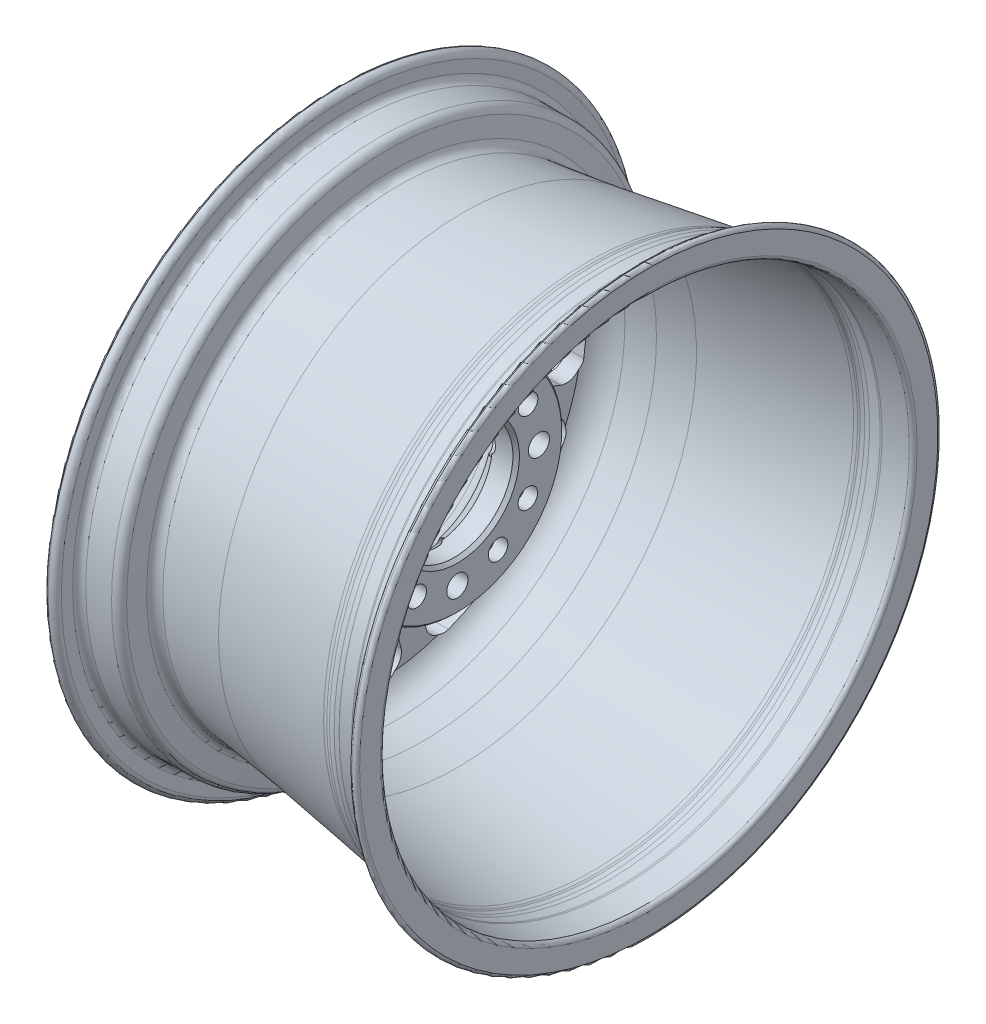
SolidWorks part; units mm, degrees
material "6061 Alloy"
ref_plane "Front Plane" through (0, 0, 0) normal (0, 0, 1) x (1, 0, 0)
ref_plane "Top Plane" through (0, 0, 0) normal (0, 1, 0) x (1, 0, 0)
ref_plane "Right Plane" through (0, 0, 0) normal (1, 0, 0) x (0, 0, -1)
sketch "Sketch1" plane through (0, 0, 0) normal (0, 0, 1) x (1, 0, 0)
  line L0 (0, 0) -> (33164.3274, 0) construction
  line L1 (0, 0) -> (0, 33164.3274) construction
  line L2 (0.0368, 178.325) -> (0.0368, 165.9849)
  line L3 (3.6882, 162.0001) -> (23.2459, 160.2891)
  line L7 (1.5368, 179.825) -> (1.8368, 179.825)
  line L8 (5.8368, 175.825) -> (5.8368, 168.825)
  line L9 (9.8368, 164.825) -> (25.6368, 164.825)
  line L19 (184.6368, 172.1546) -> (184.6368, 174.836)
  line L21 (190.6368, 177.4874) -> (190.6368, 164.7286)
  line L26 (177.3341, 164.185) -> (172.7295, 163.7822)
  line L38 (30.5561, 160.4872) -> (31.9381, 149.53)
  line L39 (37.5245, 145.195) -> (51.4368, 146.9497)
  line L42 (27.7745, 155.9302) -> (29.0697, 145.6607)
  line L43 (34.6561, 141.3257) -> (51.8723, 143.4971)
  line L46 (51.4368, 146.9497) -> (51.8723, 143.4971) construction
  line L47 (51.4368, 146.9497) -> (76.6368, 150.1281)
  line L48 (51.8723, 143.4971) -> (72.8792, 147.0647)
  line L49 (172.0635, 163.7795) -> (164.9558, 164.3453)
  line L51 (164.8368, 164.35) -> (161.8368, 164.35)
  line L52 (158.2699, 163.6704) -> (155.5589, 162.5984)
  line L53 (153.0338, 162.002) -> (76.6368, 150.1281)
  line L59 (177.5868, 161.296) -> (172.9823, 160.8932) construction
  line L60 (188.3547, 162.2381) -> (172.9823, 160.8932)
  line L61 (171.8334, 160.8887) -> (164.7812, 161.45)
  line L62 (164.7812, 161.45) -> (161.8368, 161.45)
  line L63 (159.3363, 160.9736) -> (158.3066, 160.5664)
  line L64 (156.3794, 160.0426) -> (72.8792, 147.0647)
  line L65 (153.4101, 159.5811) -> (77.0131, 147.7072) construction
  line L66 (159.3363, 160.9736) -> (156.6253, 159.9016) construction
  arc A0 (190.6368, 164.7286) -> (188.3547, 162.2381) centre (188.1368, 164.7286) cw
  arc A1 (184.6368, 172.1546) -> (177.3341, 164.185) centre (176.6368, 172.1546) cw
  arc A2 (187.9279, 179.4286) -> (184.6368, 174.836) centre (189.4868, 174.836) ccw
  arc A3 (187.9279, 179.4286) -> (190.6368, 177.4874) centre (188.5868, 177.4874) cw
  arc A12 (37.5245, 145.195) -> (31.9381, 149.53) centre (36.8988, 150.1557) cw
  arc A13 (30.5561, 160.4872) -> (25.6368, 164.825) centre (25.6368, 159.8668) ccw
  arc A14 (3.6882, 162.0001) -> (0.0368, 165.9849) centre (4.0368, 165.9849) cw
  arc A15 (9.8368, 164.825) -> (5.8368, 168.825) centre (9.8368, 168.825) cw
  arc A16 (1.8368, 179.825) -> (5.8368, 175.825) centre (1.8368, 175.825) cw
  arc A17 (1.5368, 179.825) -> (0.0368, 178.325) centre (1.5368, 178.325) ccw
  arc A20 (34.6561, 141.3257) -> (29.0697, 145.6607) centre (34.0304, 146.2864) cw
  arc A21 (27.7745, 155.9302) -> (23.2459, 160.2891) centre (22.8097, 155.304) ccw
  arc A22 (172.7295, 163.7822) -> (172.0635, 163.7795) centre (172.3809, 167.7669) cw
  arc A23 (164.9558, 164.3453) -> (164.8368, 164.35) centre (164.8368, 162.85) ccw
  arc A24 (161.8368, 164.35) -> (158.2699, 163.6704) centre (161.8368, 154.65) ccw
  arc A25 (155.5589, 162.5984) -> (153.0338, 162.002) centre (152.2494, 170.9678) cw
  arc A30 (172.9823, 160.8932) -> (171.8334, 160.8887) centre (172.3809, 167.7669) cw
  arc A31 (164.7812, 161.45) -> (164.7812, 161.45) centre (164.7812, 161.45) ccw
  arc A32 (161.8368, 161.45) -> (159.3363, 160.9736) centre (161.8368, 154.65) ccw
  arc A33 (156.3794, 160.0426) -> (158.3066, 160.5664) centre (154.9972, 168.9358) ccw
  arc A34 (156.6253, 159.9016) -> (153.2865, 159.1131) centre (152.2494, 170.9678) cw construction
  point P10 (37.7809, 148.545)
  point P22 (184.6493, 164.825)
  point P32 (172.3966, 163.753)
  point P35 (164.8964, 164.35)
  point P40 (159.9886, 164.35)
  dimension "D15" = 2.5
  dimension "D16" = 8
  dimension "D17" = 9.7
  dimension "D12" = 2.05
  dimension "D23" = 14.7
  dimension "D24" = 9
  dimension "D25" = 328.7
  dimension "D8" = 19.8
  dimension "D9" = 3
  dimension "D10" = 4
  dimension "D29" = 2.45
  dimension "D7" = 114
  dimension "D5" = 4
  dimension "D6" = 4
  dimension "D40" = 4
  dimension "D41" = 1.5
  dimension "D33" = 2.45
  dimension "D21" = 1.5
  dimension "D22" = 9.7
  dimension "D31" = 9
  dimension "D1" = 5.8
  dimension "D4" = 5
  dimension "D13" = 6
  dimension "D14" = 329.65
  dimension "D18" = 178.8
  dimension "D19" = 85
  dimension "D20" = 328.37
  dimension "D30" = 2.9
  dimension "D34" = 139.2
  dimension "D35" = 3.33
  dimension "D36" = 3.48
  dimension "D45" = 15
  dimension "D46" = 329.65
  dimension "D47" = 3.35
  dimension "D48" = 19.8
  dimension "D49" = 19.63
revolve "Revolve1" add sketch "Sketch1" angle 360 about L0
ref_plane "Plane1" through (73.2368, 0, 0) normal (1, 0, 0) x (0, 0, -1)
sketch "Sketch2" plane through (0, 0, 0) normal (0, 1, 0) x (1, 0, 0)
  line L0 (0, 0) -> (50000, 0) construction
  line L1 (0, 0) -> (0, 50000) construction
  line L2 (71.2368, 36) -> (58.7368, 36)
  line L3 (58.7368, 36) -> (48.2368, 46.5)
  line L4 (73.2368, 38) -> (73.2368, 64)
  line L5 (72.2368, 65) -> (69.5683, 65)
  line L6 (29.0697, 145.6607) -> (27.7745, 155.9302) construction
  line L8 (190.6368, -177.4874) -> (190.6368, 177.4874) construction
  line L9 (73.2368, 38) -> (71.2368, 36)
  line L10 (29.0697, 145.6607) -> (27.7745, 155.9302)
  line L12 (9.5426, 131.4781) -> (19.6126, 130.5865) construction
  line L18 (73.2368, 64) -> (72.2368, 65)
  line L20 (48.2368, 46.5) -> (19.7321, 75.0047) construction
  line L22 (9.5426, 131.4781) -> (5.7113, 88.2067)
  line L23 (17.262, 68.2791) -> (34.319, 60.4178)
  line L26 (5.7113, 88.2067) -> (23.9783, 88.2067) construction
  line L28 (19.6126, 130.5865) -> (20.6039, 98.7163)
  line L31 (32.4138, 81.0877) -> (67.5326, 65.4332)
  arc A1 (29.0697, 145.6607) -> (34.6561, 141.3257) centre (34.0304, 146.2864) ccw construction
  arc A2 (27.8741, 155.1399) -> (27.7745, 155.9302) centre (21.8846, 154.7859) ccw
  arc A3 (29.0697, 145.6607) -> (34.6561, 141.3257) centre (34.0304, 146.2864) ccw
  arc A8 (9.5426, 131.4781) -> (24.7302, 148.6092) centre (37.9429, 121.5976) cw
  arc A9 (24.7302, 148.6092) -> (27.7745, 155.9302) centre (22.0938, 153.999) ccw
  arc A10 (48.2368, 46.5) -> (34.319, 60.4178) centre (22.4209, 34.6019) ccw
  arc A11 (5.7113, 88.2067) -> (17.262, 68.2791) centre (25.6333, 86.4428) ccw
  arc A12 (34.6561, 141.3257) -> (19.6126, 130.5865) centre (37.4396, 121.5203) ccw
  arc A13 (20.6039, 98.7163) -> (32.4138, 81.0877) centre (40.5942, 99.3382) ccw
  arc A16 (69.5683, 65) -> (67.5326, 65.4332) centre (69.5683, 70) cw
  point P5 (73.2368, 36)
  point P9 (73.2368, 65)
  point P25 (10.3832, 133.6254)
  point P32 (37.9429, 121.5976)
  point P41 (33.0012, 151.2587)
  point P48 (23.9783, 88.2067)
  dimension "D11" = 262.9563
  dimension "D12" = 28.4258
  dimension "D13" = 20
  dimension "D14" = 6
  dimension "D15" = 5
  dimension "D19" = 12
  dimension "D20" = 20
  dimension "D21" = 20
  dimension "D1" = 117.4
  dimension "D2" = 72
  dimension "D3" = 45
  dimension "D4" = 2
  dimension "D5" = 45
  dimension "D6" = 130
  dimension "D7" = 25
  dimension "D8" = 10.5
  dimension "D9" = 1
  dimension "D10" = 45
  dimension "D17" = 10.07
revolve "Revolve2" add sketch "Sketch2" angle 360 about L0 region at (64.9868, 0, -37.3559)
sketch "Sketch4" plane through (73.2368, 0, 0) normal (1, 0, 0) x (0, 0, -1)
  line L0 (0, 0) -> (0, -50000) construction
  line L1 (0, 0) -> (-50000, 0) construction
  line L2 (0, 0) -> (-43301.2702, -25000) construction
  line L3 (0, 0) -> (-48296.2913, -12940.9523) construction
  line L4 (0, 0) -> (-35355.3391, -35355.3391) construction
  line L5 (0, 0) -> (-48296.2913, 12940.9523) construction
  line L6 (-94.6782, 94.3597) -> (294.6551, 94.3597) construction
  line L7 (-112.377, -43.4279) -> (-80.0541, -34.9429)
  line L8 (-80.0541, -34.9429) -> (-80.051, -34.9527) construction
  line L9 (-93.7982, -75.6073) -> (-70.2885, -51.8574)
  line L10 (-116.4914, 28.3198) -> (-88.8855, 16.2865)
  line L11 (-116.4914, -28.3198) -> (-88.8855, -16.2865)
  line L12 (-33.72, 115.0444) -> (-30.3383, 85.1204)
  line L13 (-82.7713, 86.7246) -> (-58.5473, 68.8339)
  line L14 (-93.7982, 75.6073) -> (-70.2885, 51.8574)
  line L15 (-112.377, 43.4279) -> (-80.0541, 34.9429)
  line L16 (82.7713, 86.7246) -> (58.5473, 68.8339)
  line L17 (33.72, 115.0444) -> (30.3383, 85.1204)
  line L18 (18.5788, 119.0353) -> (9.7656, 86.8003)
  line L19 (-18.5788, 119.0353) -> (-9.7656, 86.8003)
  line L20 (116.4914, -28.3198) -> (88.8855, -16.2865)
  line L21 (116.4914, 28.3198) -> (88.8855, 16.2865)
  line L22 (112.377, 43.4279) -> (80.0541, 34.9429)
  line L23 (93.7982, 75.6073) -> (70.2885, 51.8574)
  line L24 (33.72, -115.0444) -> (30.3383, -85.1204)
  line L25 (82.7713, -86.7246) -> (58.5473, -68.8339)
  line L26 (93.7982, -75.6073) -> (70.2885, -51.8574)
  line L27 (112.377, -43.4279) -> (80.0541, -34.9429)
  line L28 (-82.7713, -86.7246) -> (-58.5473, -68.8339)
  line L29 (-33.72, -115.0444) -> (-30.3383, -85.1204)
  line L30 (-18.5788, -119.0353) -> (-9.7656, -86.8003)
  line L31 (18.5788, -119.0353) -> (9.7656, -86.8003)
  line L32 (-18.5788, -119.0353) -> (-9.7656, -86.8003) [skipped]
  line L33 (18.5788, -119.0353) -> (9.7656, -86.8003) [skipped]
  line L34 (93.7982, -75.6073) -> (70.2885, -51.8574) [skipped]
  line L35 (112.377, -43.4279) -> (80.0541, -34.9429) [skipped]
  line L36 (112.377, 43.4279) -> (80.0541, 34.9429) [skipped]
  line L37 (93.7982, 75.6073) -> (70.2885, 51.8574) [skipped]
  line L38 (-18.5788, 119.0353) -> (-9.7656, 86.8003) [skipped]
  line L39 (18.5788, 119.0353) -> (9.7656, 86.8003) [skipped]
  line L40 (-93.7982, 75.6073) -> (-70.2885, 51.8574) [skipped]
  line L41 (-112.377, 43.4279) -> (-80.0541, 34.9429) [skipped]
  arc A1 (-118.841, -57.4527) -> (-109.176, -74.193) centre (0, 0) ccw
  arc A2 (-112.377, -43.4279) -> (-118.841, -57.4527) centre (-109.8379, -53.1002) ccw
  arc A3 (-47.2352, 123.2592) -> (-83.128, 102.5365) centre (0, 0) ccw
  arc A4 (-93.7982, -75.6073) -> (-109.176, -74.193) centre (-100.9051, -68.5723) cw
  arc A5 (-130.3632, 20.7227) -> (-130.3632, -20.7227) centre (0, 0) ccw
  arc A6 (-116.4914, 28.3198) -> (-130.3632, 20.7227) centre (-120.4872, 19.1528) ccw
  arc A7 (-88.8855, 16.2865) -> (-77.7999, 0) centre (-96.2709, -0.6565) cw
  arc A8 (-88.8855, -16.2865) -> (-77.7999, 0) centre (-96.2709, 0.6565) ccw
  arc A9 (-116.4914, -28.3198) -> (-130.3632, -20.7227) centre (-120.4872, -19.1528) cw
  arc A10 (-82.7713, 86.7246) -> (-83.128, 102.5365) centre (-76.8304, 94.7686) cw
  arc A11 (-33.72, 115.0444) -> (-47.2352, 123.2592) centre (-43.6568, 113.9214) ccw
  arc A12 (-30.3383, 85.1204) -> (-38.9, 67.3767) centre (-48.704, 83.0448) cw
  arc A13 (-58.5473, 68.8339) -> (-38.9, 67.3767) centre (-47.5669, 83.7013) ccw
  arc A14 (-109.176, 74.193) -> (-118.841, 57.4527) centre (0, 0) ccw
  arc A15 (-93.7982, 75.6073) -> (-109.176, 74.193) centre (-100.9051, 68.5723) ccw
  arc A16 (-70.2885, 51.8574) -> (-80.0541, 34.9429) centre (-77.4835, 44.7351) cw
  arc A17 (-112.377, 43.4279) -> (-118.841, 57.4527) centre (-109.8379, 53.1002) cw
  arc A18 (83.128, 102.5365) -> (47.2352, 123.2592) centre (0, 0) ccw
  arc A19 (33.72, 115.0444) -> (47.2352, 123.2592) centre (43.6568, 113.9214) cw
  arc A20 (82.7713, 86.7246) -> (83.128, 102.5365) centre (76.8304, 94.7686) ccw
  arc A21 (58.5473, 68.8339) -> (38.9, 67.3767) centre (47.5669, 83.7013) cw
  arc A22 (30.3383, 85.1204) -> (38.9, 67.3767) centre (48.704, 83.0448) ccw
  arc A23 (9.665, 131.6457) -> (-9.665, 131.6457) centre (0, 0) ccw
  arc A24 (18.5788, 119.0353) -> (9.665, 131.6457) centre (8.9328, 121.6725) ccw
  arc A25 (9.7656, 86.8003) -> (-9.7656, 86.8003) centre (0, 89.4703) cw
  arc A26 (-18.5788, 119.0353) -> (-9.665, 131.6457) centre (-8.9328, 121.6725) cw
  arc A27 (130.3632, -20.7227) -> (130.3632, 20.7227) centre (0, 0) ccw
  arc A28 (116.4914, 28.3198) -> (130.3632, 20.7227) centre (120.4872, 19.1528) cw
  arc A29 (116.4914, -28.3198) -> (130.3632, -20.7227) centre (120.4872, -19.1528) ccw
  arc A30 (88.8855, -16.2865) -> (77.7999, 0) centre (96.2709, 0.6565) cw
  arc A31 (88.8855, 16.2865) -> (77.7999, 0) centre (96.2709, -0.6565) ccw
  arc A32 (118.841, 57.4527) -> (109.176, 74.193) centre (0, 0) ccw
  arc A33 (112.377, 43.4279) -> (118.841, 57.4527) centre (109.8379, 53.1002) ccw
  arc A34 (80.0541, 34.9429) -> (70.2885, 51.8574) centre (77.4835, 44.7351) cw
  arc A35 (93.7982, 75.6073) -> (109.176, 74.193) centre (100.9051, 68.5723) cw
  arc A36 (47.2352, -123.2592) -> (83.128, -102.5365) centre (0, 0) ccw
  arc A37 (82.7713, -86.7246) -> (83.128, -102.5365) centre (76.8304, -94.7686) cw
  arc A38 (33.72, -115.0444) -> (47.2352, -123.2592) centre (43.6568, -113.9214) ccw
  arc A39 (30.3383, -85.1204) -> (38.9, -67.3767) centre (48.704, -83.0448) cw
  arc A40 (58.5473, -68.8339) -> (38.9, -67.3767) centre (47.5669, -83.7013) ccw
  arc A41 (109.176, -74.193) -> (118.841, -57.4527) centre (0, 0) ccw
  arc A42 (93.7982, -75.6073) -> (109.176, -74.193) centre (100.9051, -68.5723) ccw
  arc A43 (70.2885, -51.8574) -> (80.0541, -34.9429) centre (77.4835, -44.7351) cw
  arc A44 (112.377, -43.4279) -> (118.841, -57.4527) centre (109.8379, -53.1002) cw
  arc A45 (-83.128, -102.5365) -> (-47.2352, -123.2592) centre (0, 0) ccw
  arc A46 (-33.72, -115.0444) -> (-47.2352, -123.2592) centre (-43.6568, -113.9214) cw
  arc A47 (-82.7713, -86.7246) -> (-83.128, -102.5365) centre (-76.8304, -94.7686) ccw
  arc A48 (-58.5473, -68.8339) -> (-38.9, -67.3767) centre (-47.5669, -83.7013) cw
  arc A49 (-30.3383, -85.1204) -> (-38.9, -67.3767) centre (-48.704, -83.0448) ccw
  arc A50 (-9.665, -131.6457) -> (9.665, -131.6457) centre (0, 0) ccw
  arc A51 (-18.5788, -119.0353) -> (-9.665, -131.6457) centre (-8.9328, -121.6725) ccw
  arc A52 (-9.7656, -86.8003) -> (9.7656, -86.8003) centre (0, -89.4703) cw
  arc A53 (18.5788, -119.0353) -> (9.665, -131.6457) centre (8.9328, -121.6725) cw
  arc A54 (-80.0541, -34.9429) -> (-70.2885, -51.8574) centre (-77.4835, -44.7351) cw
  arc A56 (-18.5788, -119.0353) -> (-9.665, -131.6457) centre (-8.9328, -121.6725) ccw [skipped]
  arc A57 (18.5788, -119.0353) -> (9.665, -131.6457) centre (8.9328, -121.6725) cw [skipped]
  arc A58 (-9.665, -131.6457) -> (0, -132) centre (0, 0) ccw [skipped]
  arc A59 (93.7982, -75.6073) -> (109.176, -74.193) centre (100.9051, -68.5723) ccw [skipped]
  arc A60 (112.377, -43.4279) -> (118.841, -57.4527) centre (109.8379, -53.1002) cw [skipped]
  arc A61 (109.176, -74.193) -> (118.841, -57.4527) centre (0, 0) ccw [skipped]
  arc A62 (93.7982, 75.6073) -> (109.176, 74.193) centre (100.9051, 68.5723) cw [skipped]
  arc A63 (118.841, 57.4527) -> (109.176, 74.193) centre (0, 0) ccw [skipped]
  arc A64 (112.377, 43.4279) -> (118.841, 57.4527) centre (109.8379, 53.1002) ccw [skipped]
  arc A65 (18.5788, 119.0353) -> (9.665, 131.6457) centre (8.9328, 121.6725) ccw [skipped]
  arc A66 (0, 132) -> (-9.665, 131.6457) centre (0, 0) ccw [skipped]
  arc A67 (-18.5788, 119.0353) -> (-9.665, 131.6457) centre (-8.9328, 121.6725) cw [skipped]
  arc A68 (-93.7982, 75.6073) -> (-109.176, 74.193) centre (-100.9051, 68.5723) ccw [skipped]
  arc A69 (-109.176, 74.193) -> (-118.841, 57.4527) centre (0, 0) ccw [skipped]
  arc A70 (-112.377, 43.4279) -> (-118.841, 57.4527) centre (-109.8379, 53.1002) cw [skipped]
  point P31 (-127.7496, 33.2272)
  point P116 (0, 0)
  point P149 (0, 0)
  dimension "D5" = 10
  dimension "D6" = 6
  dimension "D8" = 132
  dimension "D9" = 10
  dimension "D1" = 15
  dimension "D2" = 30
  dimension "D3" = 45
  dimension "D4" = 15
  dimension "D10" = 6
extrude "Cut-Extrude1" cut sketch "Sketch4" against normal through all contours L29 A49 A48 L28 A47 A45 A46 | A9 L11 A8 A7 L10 A6 A5 | L25 A40 A39 L24 A38 A36 A37 | L21 A31 A30 L20 A29 A27 A28 | L17 A22 A21 L16 A20 A18 A19 | L13 A13 A12 L12 A11 A3 A10 | A54 L7 A2 A1 A4 L9 | A17 L15 A16 L14 A15 A14 | A26 L19 A25 L18 A24 A23 | A35 L23 A34 L22 A33 A32 | A44 L27 A43 L26 A42 A41 | A53 L31 A52 L30 A51 A50 region at (73.2368, -54.5965, 94.5639) region at (73.2368, 0, 108.6982) region at (73.2368, 94.1354, 54.3491) region at (73.2368, 54.5965, 94.5639) region at (73.2368, 94.1354, -54.3491) region at (73.2368, 109.1929, 0) region at (73.2368, 0, -108.6982) region at (73.2368, 54.5965, -94.5639) region at (73.2368, -94.1354, -54.3491) region at (73.2368, -54.5965, -94.5639) region at (73.2368, -94.1354, 54.3491) region at (73.2368, -109.1929, 0)
sketch "Sketch5" plane through (73.2368, 0, 0) normal (1, 0, 0) x (0, 0, -1)
  line L0 (0, 0) -> (0, 50000) construction
  line L1 (0, 0) -> (50000, 0) construction
hole_wizard "Ø12.0mm Dowel Hole1" positions "3DSketch1" profile "Sketch6" hole size "Ø12.0" standard "ISO"
sketch3d "3DSketch1"
  line L0 (73.2368, 0, -0.1124) -> (73.2368, 50000, -0.1124) construction
  line L1 (71.2368, 0, 0) -> (71.2368, 0, -50000) construction
  circle A0 centre (71.2368, 0, 0) radius 36 construction
  point P0 (73.2368, 49.96, -0.1124)
  point P13 (35.2368, 0, 0)
  dimension "D1" = 50
sketch "Sketch6" plane through (73.2368, 49.96, -0.1124) normal (0, 1, 0) x (0, 0, -1)
  line L0 (0, 0) -> (0, 11.6052)
  line L1 (0, 11.6052) -> (6, 8)
  line L2 (6, 8) -> (6, 0)
  line L5 (6, 0) -> (0, 0)
  line L10 (0, 11.6052) -> (-6, 8) construction
  line L11 (0, -6.35) -> (0, 107.95) construction
  dimension "Hole Dia." = 12
  dimension "Hole Depth" = 8
  dimension "Drill Angle" = 118
pattern_circular "CirPattern1" count 12 over 360 about axis through (73.2368, 0, 0) along (-1, 0, 0) of "Ø12.0mm Dowel Hole1"
ref_plane "Plane2" through (60.7368, 0, 0) normal (1, 0, 0) x (0, 0, -1)
sketch "Sketch8" plane through (73.2368, 0, 0) normal (1, 0, 0) x (0, 0, -1)
  line L0 (0, 0) -> (50000, 0) construction
  line L1 (0, 0) -> (0, 50000) construction
  circle A0 centre (0.1124, 49.96) radius 6.5
  circle A1 centre (49.96, -0.1124) radius 6.5
  circle A2 centre (-0.1124, -49.96) radius 6.5
  circle A3 centre (-49.96, 0.1124) radius 6.5
  point P17 (0, 0)
  dimension "D1" = 13
  dimension "D2" = 4
sketch "Sketch9" plane through (60.7368, 0, 0) normal (1, 0, 0) x (0, 0, -1)
  circle A0 centre (0.1124, 49.96) radius 15
  circle A1 centre (49.96, -0.1124) radius 15
  circle A2 centre (-0.1124, -49.96) radius 15
  circle A3 centre (-49.96, 0.1124) radius 15
  point P12 (0, 0)
  dimension "D1" = 30
  dimension "D2" = 4
extrude "Cut-Extrude3" cut sketch "Sketch9" against normal through all
sketch "Sketch10" plane through (60.7368, 0, 0) normal (-1, 0, 0) x (0, 0, 1)
  circle A0 centre (-0.1124, 49.96) radius 8.81
  circle A1 centre (49.96, 0.1124) radius 8.81
  circle A2 centre (0.1124, -49.96) radius 8.81
  circle A3 centre (-49.96, -0.1124) radius 8.81
  point P12 (0, 0)
  dimension "D1" = 17.62
  dimension "D2" = 4
extrude "Cut-Extrude4" cut sketch "Sketch10" against normal blind 3 draft 15
extrude "Cut-Extrude5" cut sketch "Sketch8" against normal up to surface (9.5 mm away) up to face at (63.7368, 49.96, 7.8937)
fillet "Fillet2" radius 2 4 edges at (60.7368, 64.9599, -0.1462) (60.7368, -0.1462, -64.9599) (60.7368, -64.9599, 0.1462) (60.7368, 0.1462, 64.9599)
